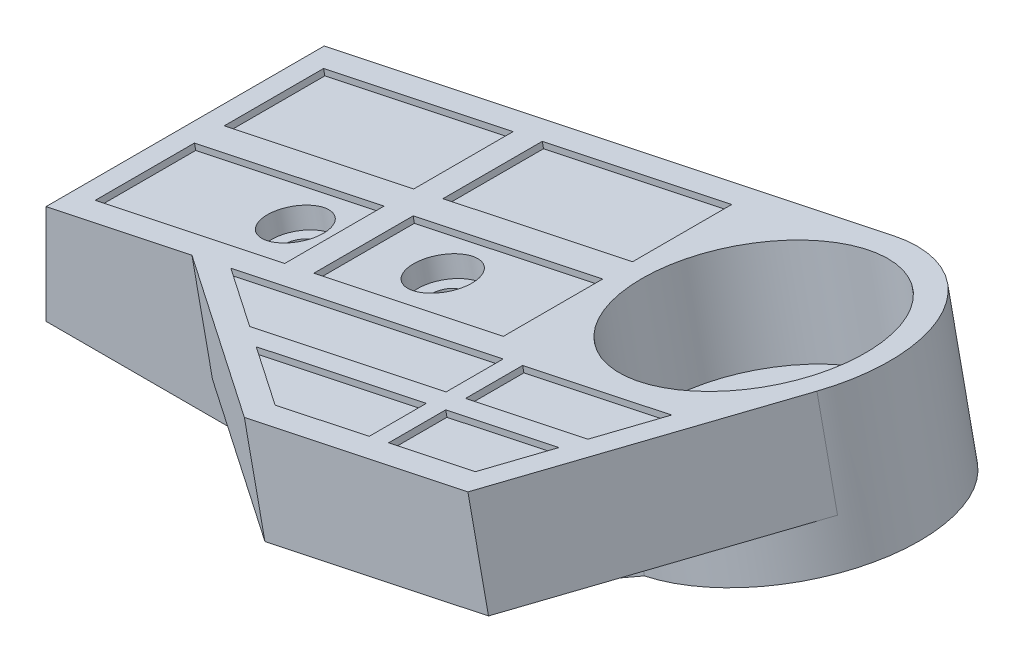
SolidWorks part; units mm, degrees
ref_plane "Alzado" through (0, 0, 0) normal (0, 0, 1) x (1, 0, 0)
ref_plane "Planta" through (0, 0, 0) normal (0, 1, 0) x (1, 0, 0)
ref_plane "Vista lateral" through (0, 0, 0) normal (1, 0, 0) x (0, 0, -1)
sketch "Croquis1" plane through (0, 0, 0) normal (0, 0, 1) x (1, 0, 0)
  line L0 (0, 0) -> (49, 0)
  line L1 (0, 0) -> (0, 10)
  line L2 (0, 10) -> (57.2341, 22.1039)
  line L3 (49, 0) -> (49, 20.3625)
  dimension "D1" = 49
  dimension "D2" = 10
  dimension "D3" = 58.5
  dimension "D4" = 101.941
extrude "Saliente-Extruir1" add sketch "Croquis1" along normal mid plane 28 contours L0 L3 L2 L1 region at (27.2872, 7.8854, 0)
sketch "Croquis3" plane through (-2.0243, 9.5719, 0) normal (-0.2069, 0.9784, 0) x (0.9784, 0.2069, 0)
  line L2 (44.319, -14) -> (60.569, -14)
  line L3 (44.319, 14) -> (60.569, 14)
  line L4 (44.319, 14) -> (44.319, -14)
  arc A0 (60.569, -14) -> (60.569, 14) centre (60.569, 0) ccw
extrude "Saliente-Extruir2" add sketch "Croquis3" against normal blind 14.497
sketch "Croquis5" plane through (0, 0, 0) normal (0, 0, 1) x (1, 0, 0)
  line L0 (49, 0) -> (49, 1.5)
  line L1 (49, 0) -> (49, 5.5449) construction
  line L2 (49, 1.5) -> (60.2337, 7.9203)
  line L3 (60.2337, 7.9203) -> (49, 6.954)
  line L4 (49, 6.954) -> (49, 1.5)
  dimension "D1" = 1.5
  dimension "D2" = 12.939
  dimension "D3" = 119.749
extrude "Saliente-Extruir3" add sketch "Croquis5" along normal mid plane 28 contours L3 L4 L2 region at (52.7446, 5.4581, 0)
sketch "Croquis6" plane through (0, 0, -14) normal (0, 0, -1) x (-1, 0, 0)
  line L0 (0, 10) -> (-14.6911, 13.1069) construction
  line L1 (0, 10) -> (-57.2341, 22.1039) construction
  line L2 (-14.6911, 13.1069) -> (-16.7601, 3.3233)
  line L3 (-16.7601, 3.3233) -> (-67.9656, 14.1522)
  line L4 (-67.9656, 14.1522) -> (-65.8965, 23.9358)
  line L5 (-57.2341, 22.1039) -> (-70.9312, 25.0006) construction
  line L6 (-65.8965, 23.9358) -> (-14.6911, 13.1069)
  dimension "D1" = 15.016
  dimension "D2" = 10
  dimension "D3" = 90
  dimension "D4" = 52.338
extrude "Saliente-Extruir4" add sketch "Croquis6" along normal blind 16
sketch "Croquis7" plane through (-2.0243, 9.5719, 0) normal (-0.2069, 0.9784, 0) x (0.9784, 0.2069, 0)
  line L0 (17.085, 14) -> (38.8336, 30)
  line L1 (17.085, 30) -> (17.085, 14) construction
  line L2 (2.069, 14) -> (17.085, 14) construction
  line L3 (17.085, 30) -> (69.423, 30) construction
  line L4 (38.8336, 30) -> (17.085, 30)
  line L5 (17.085, 30) -> (17.085, 14)
  dimension "D1" = 27
extrude "Cortar-Extruir1" cut sketch "Croquis7" against normal blind 16
sketch "Croquis8" plane through (-2.0243, 9.5719, 0) normal (-0.2069, 0.9784, 0) x (0.9784, 0.2069, 0)
  line L0 (38.8336, 30) -> (61.8336, 30)
  line L1 (38.8336, 30) -> (69.423, 30) construction
  line L2 (61.8336, 30) -> (73.218, 6.0003)
  line L3 (73.218, 6.0003) -> (73.218, 30)
  line L4 (73.218, 30) -> (61.8336, 30)
  arc A0 (60.569, -14) -> (60.569, 14) centre (60.569, 0) ccw construction
  line M11 (69.423, 14) -> (69.423, 30)
  line M12 (69.423, 30) -> (38.8336, 30)
  dimension "D1" = 23
  dimension "D2" = 26.563
extrude "Cortar-Extruir3" cut sketch "Croquis8" against normal blind 16 contours L3 L4 L2 M11 | L2 M12 M11 region at (63.4215, 23.4124, -24.6669) region at (67.8767, 24.3546, -19.8669)
sketch "Croquis9" plane through (-2.0243, 9.5719, 0) normal (-0.2069, 0.9784, 0) x (0.9784, 0.2069, 0)
  line L0 (61.8336, 30) -> (73.218, 6.0003)
  line L1 (73.218, 6.0003) -> (49.8244, 6.0003)
  line L2 (49.8244, 6.0003) -> (61.8336, 30)
  arc A0 (60.569, -14) -> (60.569, 14) centre (60.569, 0) ccw construction
  dimension "D1" = 26.563
extrude "Saliente-Extruir5" add sketch "Croquis9" against normal blind 10
sketch "Croquis10" plane through (-2.0243, 9.5719, 0) normal (-0.2069, 0.9784, 0) x (0.9784, 0.2069, 0)
  circle A0 centre (60.569, 0) radius 11.5
  dimension "D1" = 23
extrude "Cortar-Extruir4" cut sketch "Croquis10" against normal blind 10
sketch "Croquis11" plane through (0.0448, -0.2117, 0) normal (-0.2069, 0.9784, 0) x (0.9784, 0.2069, 0)
  circle A0 centre (60.569, 0) radius 1.5
  dimension "D1" = 3
extrude "Cortar-Extruir5" cut sketch "Croquis11" against normal blind 10
sketch "Croquis12" plane through (-2.0243, 9.5719, 0) normal (-0.2069, 0.9784, 0) x (0.9784, 0.2069, 0)
  line L0 (2.069, -14) -> (2.069, -11.5)
  line L1 (2.069, -14) -> (60.569, -14) construction
  line L2 (2.069, -14) -> (2.069, 14) construction
  line L3 (2.069, -11.5) -> (46.569, -11.5)
  line L4 (46.569, -11.5) -> (46.569, 11.5)
  line L5 (46.569, -11.5) -> (46.569, -1.5)
  line L6 (46.569, -1.5) -> (27.069, -1.5)
  line L7 (27.069, -1.5) -> (27.069, -11.5)
  line L8 (27.069, -1.5) -> (24.069, -1.5) construction
  line L9 (24.069, -1.5) -> (24.069, -11.5)
  line L10 (24.069, -1.5) -> (4.569, -1.5)
  line L11 (4.569, -1.5) -> (4.569, -11.5)
  line L12 (4.569, -1.5) -> (4.569, 1.5) construction
  line L13 (4.569, 1.5) -> (24.069, 1.5)
  line L14 (24.069, 1.5) -> (24.069, -1.5) construction
  line L15 (24.069, 1.5) -> (27.069, 1.5) construction
  line L16 (27.069, 1.5) -> (46.569, 1.5)
  line L17 (4.569, 1.5) -> (4.569, 11.5)
  line L18 (4.569, 11.5) -> (24.069, 11.5)
  line L19 (24.069, 11.5) -> (24.069, 1.5)
  line L20 (27.069, 1.5) -> (27.069, 11.5)
  line L21 (27.069, 11.5) -> (46.569, 11.5)
  line L22 (33.0779, 11.5) -> (33.0779, 14) construction
  line L23 (33.0779, 14) -> (21.085, 14)
  line L24 (33.0779, 14) -> (49.115, 14)
  line L25 (49.115, 14) -> (49.115, 19.75)
  line L26 (49.115, 19.75) -> (28.901, 19.75)
  line L27 (21.085, 14) -> (28.901, 19.75)
  line L28 (49.115, 14) -> (51.115, 14)
  line L29 (51.115, 14) -> (66.438, 14)
  line L30 (51.115, 14) -> (51.115, 19.75)
  line L31 (51.115, 19.75) -> (63.71, 19.75)
  line L32 (63.71, 19.75) -> (66.438, 14)
  line L33 (49.115, 19.75) -> (49.115, 21.75) construction
  line L34 (49.115, 21.75) -> (31.62, 21.75)
  line L35 (49.115, 21.75) -> (49.115, 27.5)
  line L36 (49.115, 27.5) -> (39.436, 27.5)
  line L37 (31.62, 21.75) -> (39.436, 27.5)
  line L38 (51.115, 19.75) -> (51.115, 21.75) construction
  line L39 (51.115, 21.75) -> (51.115, 27.5)
  line L40 (51.115, 27.5) -> (60.034, 27.5)
  line L41 (51.115, 21.75) -> (62.761, 21.75)
  line L42 (60.034, 27.5) -> (62.761, 21.75)
  dimension "D1" = 2.5
  dimension "D2" = 44.5
  dimension "D3" = 23
  dimension "D4" = 10
  dimension "D5" = 19.5
  dimension "D6" = 3
  dimension "D7" = 19.5
  dimension "D8" = 3
  dimension "D9" = 2.5
  dimension "D10" = 4
  dimension "D11" = 28.03
  dimension "D12" = 5.75
  dimension "D13" = 20.214
  dimension "D14" = 2
  dimension "D15" = 15.323
  dimension "D16" = 12.595
  dimension "D17" = 2
  dimension "D18" = 17.495
  dimension "D19" = 5.75
  dimension "D20" = 9.679
  dimension "D21" = 8.919
  dimension "D22" = 11.646
extrude "Cortar-Extruir6" cut sketch "Croquis12" against normal blind 0.6 contours L19 L18 L17 L13 | L10 L11 L3 L9 | L6 L7 L3 L4 | L21 L20 L16 L4 | L27 L23 L24 L25 L26 | L37 L34 L35 L36 | L42 L40 L39 L41 | L32 L31 L30 L29 region at (11.9849, 12.5346, 6.5) region at (33.9981, 17.1899, -6.5) region at (33.9981, 17.1899, 6.5) region at (11.9849, 12.5346, -6.5) region at (54.8349, 21.5965, -16.7814) region at (34.1247, 17.2167, -16.7197) region at (39.1982, 18.2897, -24.3494) region at (53.0442, 21.2178, -24.4979)
sketch "Croquis13" plane through (-1.9001, 8.9849, 0) normal (-0.2069, 0.9784, 0) x (0.9784, 0.2069, 0)
  line L0 (27.069, 1.5) -> (27.069, 11.5) construction
  line L1 (27.069, 1.5) -> (46.569, 1.5) construction
  circle A0 centre (34.584, 6) radius 3.0005
  dimension "D2" = 4.5
  dimension "D3" = 6.001
  dimension "D1" = 7.515
extrude "Cortar-Extruir7" cut sketch "Croquis13" against normal blind 2
sketch "Croquis14" plane through (-1.4863, 7.0282, 0) normal (-0.2069, 0.9784, 0) x (0.9784, 0.2069, 0)
  circle A0 centre (34.584, 6) radius 1.5
  dimension "D1" = 3
extrude "Cortar-Extruir8" cut sketch "Croquis14" against normal through all
sketch "Croquis15" plane through (-1.9001, 8.9849, 0) normal (-0.2069, 0.9784, 0) x (0.9784, 0.2069, 0)
  line L0 (24.069, 11.5) -> (24.069, 1.5) construction
  line L1 (4.569, 11.5) -> (24.069, 11.5) construction
  circle A0 centre (19.384, 5.967) radius 2.8798
  dimension "D1" = 4.685
  dimension "D2" = 5.533
extrude "Cortar-Extruir9" cut sketch "Croquis15" against normal blind 2
sketch "Croquis16" plane through (-1.4863, 7.0282, 0) normal (-0.2069, 0.9784, 0) x (0.9784, 0.2069, 0)
  circle A0 centre (19.384, 5.967) radius 1.5
  dimension "D1" = 3
extrude "Cortar-Extruir10" cut sketch "Croquis16" against normal through all
mirror "Simetría1" about plane through (0, 0, 14) normal (0, 0, 1) of "Saliente-Extruir5", "Saliente-Extruir1", "Cortar-Extruir3", "Cortar-Extruir4", "Cortar-Extruir5", "Cortar-Extruir6", "Cortar-Extruir7", "Cortar-Extruir8", "Cortar-Extruir9", "Cortar-Extruir10", "Saliente-Extruir4", "Cortar-Extruir1", "Saliente-Extruir3", "Saliente-Extruir2"
sketch "Croquis17" plane through (-2.0243, 9.5719, 0) normal (-0.2069, 0.9784, 0) x (0.9784, 0.2069, 0)
  line L0 (60.569, -14) -> (2.069, -14)
  line L1 (2.069, -42) -> (2.069, 14) construction
  line L3 (2.069, 46.0527) -> (94.2265, 46.0527)
  line L4 (94.2265, 46.0527) -> (94.2265, -14)
  line L5 (94.2265, -14) -> (60.569, -14)
  line L6 (2.069, -14) -> (-8.3747, -14)
  line L7 (-8.3747, -14) -> (-8.3747, 46.0527)
  line L8 (-8.3747, 46.0527) -> (2.069, 46.0527)
extrude "Cortar-Extruir11" cut sketch "Croquis17" against normal through all
